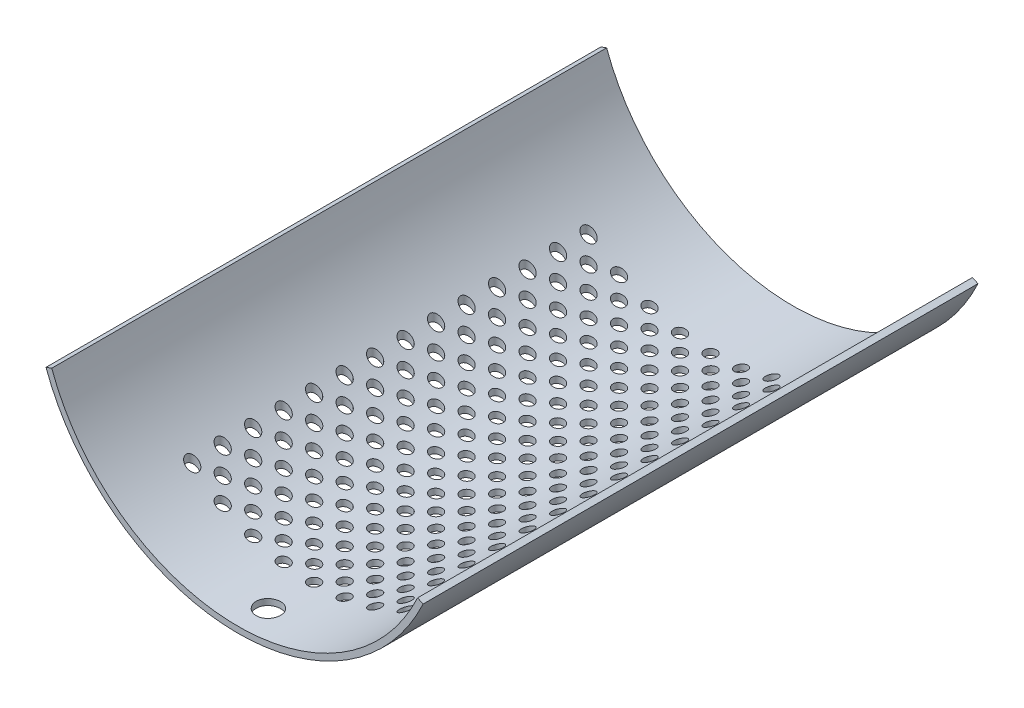
SolidWorks part; units mm, degrees
ref_plane "Front Plane" through (0, 0, 0) normal (0, 0, 1) x (1, 0, 0)
ref_plane "Top Plane" through (0, 0, 0) normal (0, 1, 0) x (1, 0, 0)
ref_plane "Right Plane" through (0, 0, 0) normal (1, 0, 0) x (0, 0, -1)
sketch "Sketch1" plane through (0, 0, 0) normal (0, 0, 1) x (1, 0, 0)
  line L0 (0, 82.628) -> (0, -96.3347) construction
  line L1 (0, 0) -> (-119.5442, -43.5105) construction
  line L2 (0, 0) -> (127.1223, -59.2781) construction
  line L3 (-61.08, -22.2313) -> (-62.9594, -22.9153)
  line L4 (58.91, -27.4702) -> (60.7226, -28.3154)
  arc A0 (-61.08, -22.2313) -> (58.91, -27.4702) centre (0, 0) ccw
  arc A1 (-62.9594, -22.9153) -> (60.7226, -28.3154) centre (0, 0) ccw
  dimension "D3" = 70
  dimension "D1" = 67
  dimension "D2" = 65
  dimension "D4" = 2
extrude "Boss-Extrude1" add sketch "Sketch1" along normal blind 170 and the other way blind 12
sketch "Sketch2" plane through (0, 0, 0) normal (0, 1, 0) x (1, 0, 0)
  line L0 (-61.08, -170) -> (58.91, -170) construction
  line L1 (-61.08, -170) -> (58.91, -170) construction
  line L2 (0, -170) -> (0, -145) construction
  line L5 (23.5396, -140) -> (48.3962, -140) construction
  line L6 (35, -130.7921) -> (35, -152.4497) construction
  circle A637 centre (0, -145) radius 2
  circle A638 centre (10, -145) radius 2
  circle A639 centre (20, -145) radius 2
  circle A640 centre (30, -145) radius 2
  circle A641 centre (40, -145) radius 2
  circle A642 centre (10, -135) radius 2
  circle A643 centre (20, -135) radius 2
  circle A644 centre (30, -135) radius 2
  circle A645 centre (40, -135) radius 2
  circle A646 centre (10, -125) radius 2
  circle A647 centre (20, -125) radius 2
  circle A648 centre (30, -125) radius 2
  circle A649 centre (40, -125) radius 2
  circle A650 centre (10, -115) radius 2
  circle A651 centre (20, -115) radius 2
  circle A652 centre (30, -115) radius 2
  circle A653 centre (40, -115) radius 2
  circle A654 centre (10, -105) radius 2
  circle A655 centre (20, -105) radius 2
  circle A656 centre (30, -105) radius 2
  circle A657 centre (40, -105) radius 2
  circle A658 centre (10, -95) radius 2
  circle A659 centre (20, -95) radius 2
  circle A660 centre (30, -95) radius 2
  circle A661 centre (40, -95) radius 2
  circle A662 centre (10, -85) radius 2
  circle A663 centre (20, -85) radius 2
  circle A664 centre (30, -85) radius 2
  circle A665 centre (40, -85) radius 2
  circle A666 centre (10, -75) radius 2
  circle A667 centre (20, -75) radius 2
  circle A668 centre (30, -75) radius 2
  circle A669 centre (40, -75) radius 2
  circle A670 centre (10, -65) radius 2
  circle A671 centre (20, -65) radius 2
  circle A672 centre (30, -65) radius 2
  circle A673 centre (40, -65) radius 2
  circle A674 centre (10, -55) radius 2
  circle A675 centre (20, -55) radius 2
  circle A676 centre (30, -55) radius 2
  circle A677 centre (40, -55) radius 2
  circle A678 centre (10, -45) radius 2
  circle A679 centre (20, -45) radius 2
  circle A680 centre (30, -45) radius 2
  circle A681 centre (40, -45) radius 2
  circle A682 centre (10, -35) radius 2
  circle A683 centre (20, -35) radius 2
  circle A684 centre (30, -35) radius 2
  circle A685 centre (40, -35) radius 2
  circle A686 centre (10, -25) radius 2
  circle A687 centre (20, -25) radius 2
  circle A688 centre (30, -25) radius 2
  circle A689 centre (40, -25) radius 2
  circle A690 centre (10, -15) radius 2
  circle A691 centre (20, -15) radius 2
  circle A692 centre (30, -15) radius 2
  circle A693 centre (40, -15) radius 2
  circle A694 centre (0, -135) radius 2
  circle A695 centre (0, -125) radius 2
  circle A696 centre (0, -115) radius 2
  circle A697 centre (0, -105) radius 2
  circle A698 centre (0, -95) radius 2
  circle A699 centre (0, -85) radius 2
  circle A700 centre (0, -75) radius 2
  circle A701 centre (0, -65) radius 2
  circle A702 centre (0, -55) radius 2
  circle A703 centre (0, -45) radius 2
  circle A704 centre (0, -35) radius 2
  circle A705 centre (0, -25) radius 2
  circle A706 centre (0, -15) radius 2
  circle A707 centre (0, -160) radius 4
  circle A708 centre (-10, -145) radius 2
  circle A709 centre (-20, -145) radius 2
  circle A710 centre (-30, -145) radius 2
  circle A711 centre (-40, -145) radius 2
  circle A712 centre (-10, -135) radius 2
  circle A713 centre (-20, -135) radius 2
  circle A714 centre (-30, -135) radius 2
  circle A715 centre (-40, -135) radius 2
  circle A716 centre (-10, -125) radius 2
  circle A717 centre (-20, -125) radius 2
  circle A718 centre (-30, -125) radius 2
  circle A719 centre (-40, -125) radius 2
  circle A720 centre (-10, -115) radius 2
  circle A721 centre (-20, -115) radius 2
  circle A722 centre (-30, -115) radius 2
  circle A723 centre (-40, -115) radius 2
  circle A724 centre (-10, -105) radius 2
  circle A725 centre (-20, -105) radius 2
  circle A726 centre (-30, -105) radius 2
  circle A727 centre (-40, -105) radius 2
  circle A728 centre (-10, -95) radius 2
  circle A729 centre (-20, -95) radius 2
  circle A730 centre (-30, -95) radius 2
  circle A731 centre (-40, -95) radius 2
  circle A732 centre (-10, -85) radius 2
  circle A733 centre (-20, -85) radius 2
  circle A734 centre (-30, -85) radius 2
  circle A735 centre (-40, -85) radius 2
  circle A736 centre (-10, -75) radius 2
  circle A737 centre (-20, -75) radius 2
  circle A738 centre (-30, -75) radius 2
  circle A739 centre (-40, -75) radius 2
  circle A740 centre (-10, -65) radius 2
  circle A741 centre (-20, -65) radius 2
  circle A742 centre (-30, -65) radius 2
  circle A743 centre (-40, -65) radius 2
  circle A744 centre (-10, -55) radius 2
  circle A745 centre (-20, -55) radius 2
  circle A746 centre (-30, -55) radius 2
  circle A747 centre (-40, -55) radius 2
  circle A748 centre (-10, -45) radius 2
  circle A749 centre (-20, -45) radius 2
  circle A750 centre (-30, -45) radius 2
  circle A751 centre (-40, -45) radius 2
  circle A752 centre (-10, -35) radius 2
  circle A753 centre (-20, -35) radius 2
  circle A754 centre (-30, -35) radius 2
  circle A755 centre (-40, -35) radius 2
  circle A756 centre (-10, -25) radius 2
  circle A757 centre (-20, -25) radius 2
  circle A758 centre (-30, -25) radius 2
  circle A759 centre (-40, -25) radius 2
  circle A760 centre (-10, -15) radius 2
  circle A761 centre (-20, -15) radius 2
  circle A762 centre (-30, -15) radius 2
  circle A763 centre (-40, -15) radius 2
  circle A764 centre (0, -135) radius 2
  circle A765 centre (0, -125) radius 2
  circle A766 centre (0, -115) radius 2
  circle A767 centre (0, -105) radius 2
  circle A768 centre (0, -95) radius 2
  circle A769 centre (0, -85) radius 2
  circle A770 centre (0, -75) radius 2
  circle A771 centre (0, -65) radius 2
  circle A772 centre (0, -55) radius 2
  circle A773 centre (0, -45) radius 2
  circle A774 centre (0, -35) radius 2
  circle A775 centre (0, -25) radius 2
  circle A776 centre (0, -15) radius 2
  circle A777 centre (35, -140) radius 2
  circle A778 centre (25, -140) radius 2
  circle A779 centre (15, -140) radius 2
  circle A780 centre (5, -140) radius 2
  circle A781 centre (-5, -140) radius 2
  circle A782 centre (-15, -140) radius 2
  circle A783 centre (-25, -140) radius 2
  circle A784 centre (-35, -140) radius 2
  circle A785 centre (25, -130) radius 2
  circle A786 centre (15, -130) radius 2
  circle A787 centre (5, -130) radius 2
  circle A788 centre (-5, -130) radius 2
  circle A789 centre (-15, -130) radius 2
  circle A790 centre (-25, -130) radius 2
  circle A791 centre (-35, -130) radius 2
  circle A792 centre (25, -120) radius 2
  circle A793 centre (15, -120) radius 2
  circle A794 centre (5, -120) radius 2
  circle A795 centre (-5, -120) radius 2
  circle A796 centre (-15, -120) radius 2
  circle A797 centre (-25, -120) radius 2
  circle A798 centre (-35, -120) radius 2
  circle A799 centre (25, -110) radius 2
  circle A800 centre (15, -110) radius 2
  circle A801 centre (5, -110) radius 2
  circle A802 centre (-5, -110) radius 2
  circle A803 centre (-15, -110) radius 2
  circle A804 centre (-25, -110) radius 2
  circle A805 centre (-35, -110) radius 2
  circle A806 centre (25, -100) radius 2
  circle A807 centre (15, -100) radius 2
  circle A808 centre (5, -100) radius 2
  circle A809 centre (-5, -100) radius 2
  circle A810 centre (-15, -100) radius 2
  circle A811 centre (-25, -100) radius 2
  circle A812 centre (-35, -100) radius 2
  circle A813 centre (25, -90) radius 2
  circle A814 centre (15, -90) radius 2
  circle A815 centre (5, -90) radius 2
  circle A816 centre (-5, -90) radius 2
  circle A817 centre (-15, -90) radius 2
  circle A818 centre (-25, -90) radius 2
  circle A819 centre (-35, -90) radius 2
  circle A820 centre (25, -80) radius 2
  circle A821 centre (15, -80) radius 2
  circle A822 centre (5, -80) radius 2
  circle A823 centre (-5, -80) radius 2
  circle A824 centre (-15, -80) radius 2
  circle A825 centre (-25, -80) radius 2
  circle A826 centre (-35, -80) radius 2
  circle A827 centre (25, -70) radius 2
  circle A828 centre (15, -70) radius 2
  circle A829 centre (5, -70) radius 2
  circle A830 centre (-5, -70) radius 2
  circle A831 centre (-15, -70) radius 2
  circle A832 centre (-25, -70) radius 2
  circle A833 centre (-35, -70) radius 2
  circle A834 centre (25, -60) radius 2
  circle A835 centre (15, -60) radius 2
  circle A836 centre (5, -60) radius 2
  circle A837 centre (-5, -60) radius 2
  circle A838 centre (-15, -60) radius 2
  circle A839 centre (-25, -60) radius 2
  circle A840 centre (-35, -60) radius 2
  circle A841 centre (25, -50) radius 2
  circle A842 centre (15, -50) radius 2
  circle A843 centre (5, -50) radius 2
  circle A844 centre (-5, -50) radius 2
  circle A845 centre (-15, -50) radius 2
  circle A846 centre (-25, -50) radius 2
  circle A847 centre (-35, -50) radius 2
  circle A848 centre (25, -40) radius 2
  circle A849 centre (15, -40) radius 2
  circle A850 centre (5, -40) radius 2
  circle A851 centre (-5, -40) radius 2
  circle A852 centre (-15, -40) radius 2
  circle A853 centre (-25, -40) radius 2
  circle A854 centre (-35, -40) radius 2
  circle A855 centre (25, -30) radius 2
  circle A856 centre (15, -30) radius 2
  circle A857 centre (5, -30) radius 2
  circle A858 centre (-5, -30) radius 2
  circle A859 centre (-15, -30) radius 2
  circle A860 centre (-25, -30) radius 2
  circle A861 centre (-35, -30) radius 2
  circle A862 centre (25, -20) radius 2
  circle A863 centre (15, -20) radius 2
  circle A864 centre (5, -20) radius 2
  circle A865 centre (-5, -20) radius 2
  circle A866 centre (-15, -20) radius 2
  circle A867 centre (-25, -20) radius 2
  circle A868 centre (-35, -20) radius 2
  circle A869 centre (35, -130) radius 2
  circle A870 centre (35, -120) radius 2
  circle A871 centre (35, -110) radius 2
  circle A872 centre (35, -100) radius 2
  circle A873 centre (35, -90) radius 2
  circle A874 centre (35, -80) radius 2
  circle A875 centre (35, -70) radius 2
  circle A876 centre (35, -60) radius 2
  circle A877 centre (35, -50) radius 2
  circle A878 centre (35, -40) radius 2
  circle A879 centre (35, -30) radius 2
  circle A880 centre (35, -20) radius 2
  dimension "D3" = 5
  dimension "D4" = 14
  dimension "D1" = 25
  dimension "D2" = 4
  dimension "D5" = 8
  dimension "D11" = 4
  dimension "D7" = 5
  dimension "D10" = 5
  dimension "D6" = 10
  dimension "D9" = 5
  dimension "D8" = 14
  dimension "D12" = 8
  dimension "D13" = 13
extrude "Cut-Extrude1" cut sketch "Sketch2" against normal blind 90
